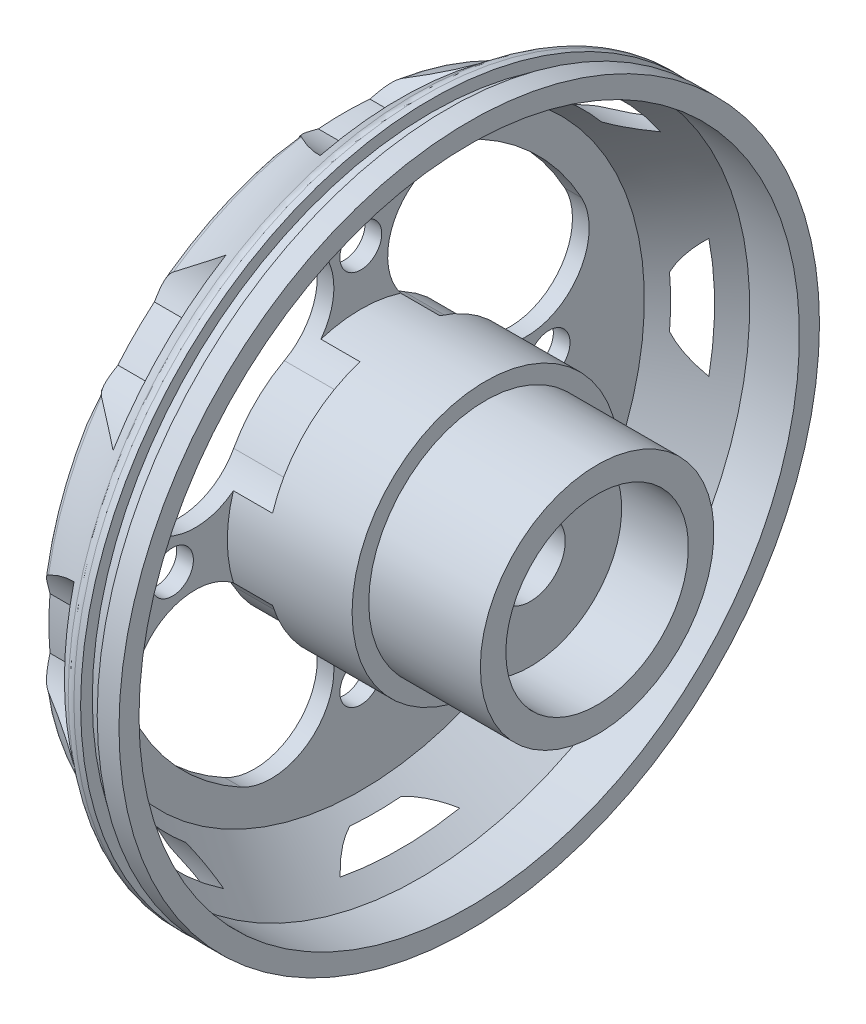
SolidWorks part; units mm, degrees
ref_plane "Front Plane" through (0, 0, 0) normal (0, 0, 1) x (1, 0, 0)
ref_plane "Top Plane" through (0, 0, 0) normal (0, 1, 0) x (1, 0, 0)
ref_plane "Right Plane" through (0, 0, 0) normal (1, 0, 0) x (0, 0, -1)
sketch "Sketch1" plane through (0, 0, 0) normal (0, 0, 1) x (1, 0, 0)
  line L0 (0, 30.9048) -> (0, 0) construction
  line L1 (0, 0) -> (41.2543, 0) construction
  line L3 (13.355, 6.545) -> (13.355, 2.5)
  line L4 (13.355, 2.5) -> (4.784, 2.5)
  line L5 (4.784, 2.5) -> (4.784, 6.545)
  line L6 (4.784, 6.545) -> (0, 6.545)
  line L7 (0, 6.545) -> (0, 21.815)
  line L8 (5.382, 25.11) -> (6.2192, 25.11)
  line L10 (1.196, 20.332) -> (1.196, 9.568)
  line L11 (1.196, 9.568) -> (10.139, 9.568)
  line L12 (10.139, 9.568) -> (10.139, 8.372)
  line L17 (18.139, 6.545) -> (13.355, 6.545)
  line L18 (10.139, 8.372) -> (18.139, 8.372)
  line L19 (18.139, 8.372) -> (18.139, 6.545)
  line L20 (8.97, 25.11) -> (8.97, 23.6748)
  line L21 (8.97, 23.6748) -> (5.4, 23.6748)
  line L23 (1.196, 20.332) -> (5.4, 23.6748)
  line L24 (7.4092, 25.11) -> (8.97, 25.11)
  line L26 (6.2192, 25.11) -> (6.2192, 24.2728)
  line L27 (6.2192, 24.2728) -> (7.4092, 24.2728)
  line L28 (7.4092, 25.11) -> (7.4092, 24.2728)
  arc A0 (5.382, 25.11) -> (0, 21.815) centre (-8.5797, 41.8721) cw
  point P3 (1.196, 14.95)
  dimension "D12" = 5.382
  dimension "D18" = 21.815
  dimension "D19" = 21.815
  dimension "D1" = 22.61
  dimension "D2" = 5.355
  dimension "D3" = 2.5
  dimension "D4" = 9.568
  dimension "D5" = 4.784
  dimension "D6" = 8.372
  dimension "D7" = 4.784
  dimension "D8" = 6.545
  dimension "D9" = 1.4352
  dimension "D10" = 3.588
  dimension "D11" = 1.196
  dimension "D13" = 10.764
  dimension "D14" = 3.57
  dimension "D15" = 1.19
  dimension "D16" = 0.8372
  dimension "D17" = 0.8372
  dimension "D20" = 8
revolve "Revolve1" add sketch "Sketch1" angle 360 about L1
fillet "Fillet1" radius 1 2 edges at (5.382, 0, 25.11) (0, 0, 21.815)
sketch "Sketch2" plane through (0, 0, 0) normal (-1, 0, 0) x (0, 0, 1)
  line L0 (0, 24.8885) -> (0, 0) construction
  line L1 (0, 0) -> (24.8885, 0) construction
  line L2 (0, 0) -> (17.5988, 17.5988) construction
  circle A0 centre (0, 0) radius 24.8885 construction
  arc A1 (6.4272, 11.8719) -> (11.8719, 6.4272) centre (0, 0) cw construction
  arc A2 (15.8292, 8.5695) -> (8.5695, 15.8292) centre (0, 0) ccw
  arc A3 (7.9146, 4.2848) -> (4.2848, 7.9146) centre (0, 0) ccw
  arc A4 (7.9146, 4.2848) -> (15.8292, 8.5695) centre (11.8719, 6.4272) ccw
  arc A5 (8.5695, 15.8292) -> (4.2848, 7.9146) centre (6.4272, 11.8719) ccw
  arc A6 (11.8719, -6.4272) -> (6.4272, -11.8719) centre (0, 0) cw construction
  arc A7 (8.5695, -15.8292) -> (15.8292, -8.5695) centre (0, 0) ccw
  arc A8 (4.2848, -7.9146) -> (7.9146, -4.2848) centre (0, 0) ccw
  arc A9 (4.2848, -7.9146) -> (8.5695, -15.8292) centre (6.4272, -11.8719) ccw
  arc A10 (15.8292, -8.5695) -> (7.9146, -4.2848) centre (11.8719, -6.4272) ccw
  arc A11 (-6.4272, -11.8719) -> (-11.8719, -6.4272) centre (0, 0) cw construction
  arc A12 (-15.8292, -8.5695) -> (-8.5695, -15.8292) centre (0, 0) ccw
  arc A13 (-7.9146, -4.2848) -> (-4.2848, -7.9146) centre (0, 0) ccw
  arc A14 (-7.9146, -4.2848) -> (-15.8292, -8.5695) centre (-11.8719, -6.4272) ccw
  arc A15 (-8.5695, -15.8292) -> (-4.2848, -7.9146) centre (-6.4272, -11.8719) ccw
  arc A16 (-11.8719, 6.4272) -> (-6.4272, 11.8719) centre (0, 0) cw construction
  arc A17 (-8.5695, 15.8292) -> (-15.8292, 8.5695) centre (0, 0) ccw
  arc A18 (-4.2848, 7.9146) -> (-7.9146, 4.2848) centre (0, 0) ccw
  arc A19 (-4.2848, 7.9146) -> (-8.5695, 15.8292) centre (-6.4272, 11.8719) ccw
  arc A20 (-15.8292, 8.5695) -> (-7.9146, 4.2848) centre (-11.8719, 6.4272) ccw
  arc A21 (12.6074, 21.7156) -> (21.7156, 12.6074) centre (20.2595, 20.2595) ccw
  circle A22 centre (0, 0) radius 25.11 construction
  arc A23 (24.27, 6.4405) -> (24.27, -6.4405) centre (28.6513, 0) ccw
  arc A24 (21.7156, -12.6074) -> (12.6074, -21.7156) centre (20.2595, -20.2595) ccw
  arc A25 (6.4405, -24.27) -> (-6.4405, -24.27) centre (0, -28.6513) ccw
  arc A26 (-12.6074, -21.7156) -> (-21.7156, -12.6074) centre (-20.2595, -20.2595) ccw
  arc A27 (-24.27, -6.4405) -> (-24.27, 6.4405) centre (-28.6513, 0) ccw
  arc A28 (-21.7156, 12.6074) -> (-12.6074, 21.7156) centre (-20.2595, 20.2595) ccw
  arc A29 (-6.4405, 24.27) -> (6.4405, 24.27) centre (0, 28.6513) ccw
  circle A30 centre (0, 0) radius 25.11
  point P10 (9.5459, 9.5459)
  point P20 (9.5459, -9.5459)
  point P27 (-9.5459, -9.5459)
  point P34 (-9.5459, 9.5459)
  point P39 (0, 0)
  point P67 (0, 0)
  circle M14 centre (0, 0) radius 21.1657
  dimension "D2" = 9
  dimension "D3" = 18
  dimension "D1" = 7.7
  dimension "D4" = 4
  dimension "D5" = 8
extrude "Cut-Extrude2" cut sketch "Sketch2" against normal blind 4 contours A28 A30 M14 | A29 A30 M14 | A21 A30 M14 | A23 A30 M14 | A24 A30 M14 | A25 A30 M14 | A26 A30 M14 | A27 A30 M14 | A17 A20 A18 A19 | A2 A5 A3 A4 | A7 A10 A8 A9 | A12 A15 A13 A14 region at (0, 9.288, 9.288) region at (0, -9.288, 9.288) region at (0, -9.288, -9.288) region at (0, 9.288, -9.288) region at (0, 16.4401, 16.4401) region at (0, 23.2499, 0) region at (0, 0, 23.2499) region at (0, 16.4401, -16.4401) region at (0, -16.4401, 16.4401) region at (0, 0, -23.2499) region at (0, -23.2499, 0) region at (0, -16.4401, -16.4401)
sketch "Sketch3" plane through (0, 0, 0) normal (-1, 0, 0) x (0, 0, 1)
  circle A0 centre (0, 0) radius 13.5 construction
  circle A1 centre (0, 13.5) radius 1.5
  circle A2 centre (13.5, 0) radius 1.5
  circle A3 centre (0, -13.5) radius 1.5
  circle A4 centre (-13.5, 0) radius 1.5
  point P15 (0, 0)
  dimension "D2" = 3
  dimension "D1" = 4
extrude "Cut-Extrude3" cut sketch "Sketch3" against normal blind 4
